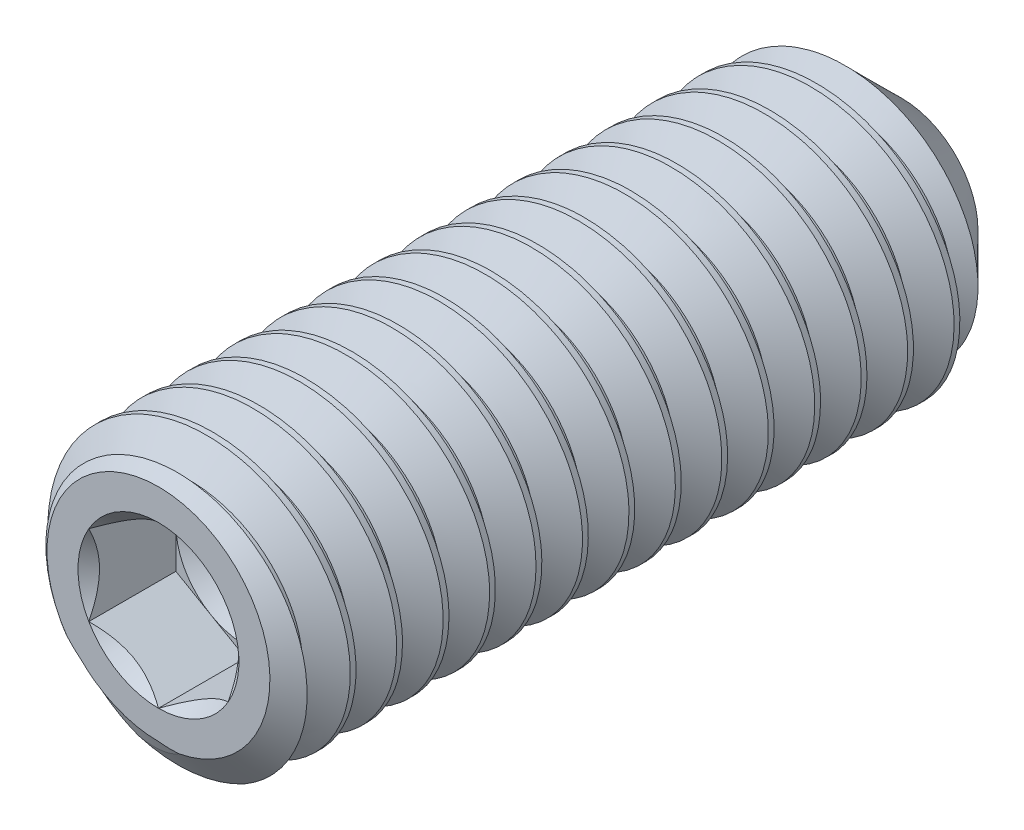
SolidWorks part; units mm, degrees
material "Cast Stainless Steel"
ref_plane "Front" through (0, 0, 0) normal (0, 0, 1) x (1, 0, 0)
ref_plane "Top" through (0, 0, 0) normal (0, 1, 0) x (1, 0, 0)
ref_plane "Right" through (0, 0, 0) normal (1, 0, 0) x (0, 0, -1)
sketch "Sketch22" plane through (0, 0, 0) normal (1, 0, 0) x (0, 0, -1)
  line L0 (-7.5061, 0) -> (-7.5061, 2.4)
  line L1 (-7.5061, 2.4) -> (-7.086, 3)
  line L2 (-7.086, 3) -> (7.1378, 3)
  line L3 (7.1378, 3) -> (8.4939, 1.6439)
  line L4 (8.4939, 1.6439) -> (7.5061, 0)
  line L5 (7.5061, 0) -> (-7.5061, 0)
  line L6 (7.5061, 0) -> (8.4939, 0) construction
  line L7 (8.4939, 0) -> (8.4939, 1.6439) construction
  line L8 (8.4939, -1.6439) -> (7.5061, 0) construction
  line L9 (-7.086, -3) -> (7.1378, -3) construction
  dimension "Dia" = 6
  dimension "Length" = 16
  dimension "D3" = 35
  dimension "D5" = 118
  dimension "D6" = 45
  dimension "D7" = 4.8
revolve "Revolve1" add sketch "Sketch22" angle 360 about L6
ref_plane "Plane1" through (0, 0, -8.4939) normal (0, 0, 1) x (1, 0, 0)
sketch "Sketch27" plane through (0, 0, -8.4939) normal (0, 0, 1) x (1, 0, 0)
  circle A0 centre (0, 0) radius 3 construction
  circle A1 centre (0, 0) radius 3
curve "Helix/Spiral1" pitch 1 height 17 radius 3 centre (0, 0, -8.4939) axis (0, 0, 1) start towards (0, 1, 0)
sketch "Sketch28" plane through (0, 0, 0) normal (1, 0, 0) x (0, 0, -1)
  line L0 (8.4939, 3) -> (9.3689, 3)
  line L1 (9.3689, 3) -> (8.9939, 2.3505)
  line L2 (8.9939, 2.3505) -> (8.8689, 2.3505)
  line L3 (8.8689, 2.3505) -> (8.4939, 3)
  line L4 (8.6814, 2.6752) -> (9.1814, 2.6752) construction
  line L6 (-7.086, 3) -> (7.1378, 3) construction
  dimension "D1" = 0.125
  dimension "D3" = 60
  dimension "D2" = 0.5
sweep "Cut-Sweep2" cut profiles "Sketch28" path "Helix/Spiral1" align with end faces yes
sketch "Sketch23" plane through (0, 0, 7.5061) normal (0, 0, 1) x (1, 0, 0)
  line L1 (0, 1.7321) -> (-1.5, 0.866)
  line L2 (-1.5, 0.866) -> (-1.5, -0.866)
  line L3 (-1.5, -0.866) -> (0, -1.7321)
  line L4 (0, -1.7321) -> (1.5, -0.866)
  line L5 (1.5, -0.866) -> (1.5, 0.866)
  line L6 (1.5, 0.866) -> (0, 1.7321)
  circle A0 centre (0, 0) radius 1.5 construction
  dimension "Hex" = 3
extrude "Cut-Extrude10" cut sketch "Sketch23" against normal blind 1.875
sketch "Sketch24" plane through (0, 0, 7.5061) normal (0, 0, 1) x (1, 0, 0)
  circle A0 centre (0, 0) radius 1.7321
extrude "Cut-Extrude11" cut sketch "Sketch24" against normal through all draft 45
sketch "Sketch26" plane through (0, 0, 5.6311) normal (0, 0, 1) x (1, 0, 0)
  circle A0 centre (0, 0) radius 1.5 construction
  circle A1 centre (0, 0) radius 1.5
extrude "Cut-Extrude12" cut sketch "Sketch26" against normal through all draft 60
sketch "Sketch30" plane through (0, 0, 0) normal (1, 0, 0) x (0, 0, -1)
  line L0 (-7.086, 3) -> (7.1378, 3) construction
  line L1 (-7.5061, 0) -> (-7.5061, 2.4) construction
  line L2 (8.4939, 0) -> (8.4939, 1.6439) construction
  line L3 (-7.086, -3) -> (7.1378, -3) construction
  point P0 (-7.5061, 3)
  point P1 (8.4939, 3)
  point P2 (8.4939, -3)
  point P11 (6.9939, -3)
  dimension "D1" = 1.5
sketch "Sketch31" plane through (0, 0, 0) normal (1, 0, 0) x (0, 0, -1)
  line L2 (7.5061, 0) -> (8.4939, -1.6439)
  line L3 (8.4939, 1.6439) -> (7.5061, 0)
move or copy body "Body-Move/Copy1" [suppressed] bodies to move or copy 161
equation "\"D7@Sketch22\"=\"Dia@Sketch22\"*.8"
equation "\"D1@Sketch28\" = \"D4@Helix/Spiral1\" * .125"
equation "\"D2@Sketch28\" = \"D4@Helix/Spiral1\" * .5"
equation "\"D3@Helix/Spiral1\" = \"Length@Sketch22\" + \"D4@Helix/Spiral1\""
equation "\"D1@Sketch30\" = \"D4@Helix/Spiral1\" * 1.5"
equation "\"hex Depth@Cut-Extrude10\" = \"Hex@Sketch23\" * .625"
